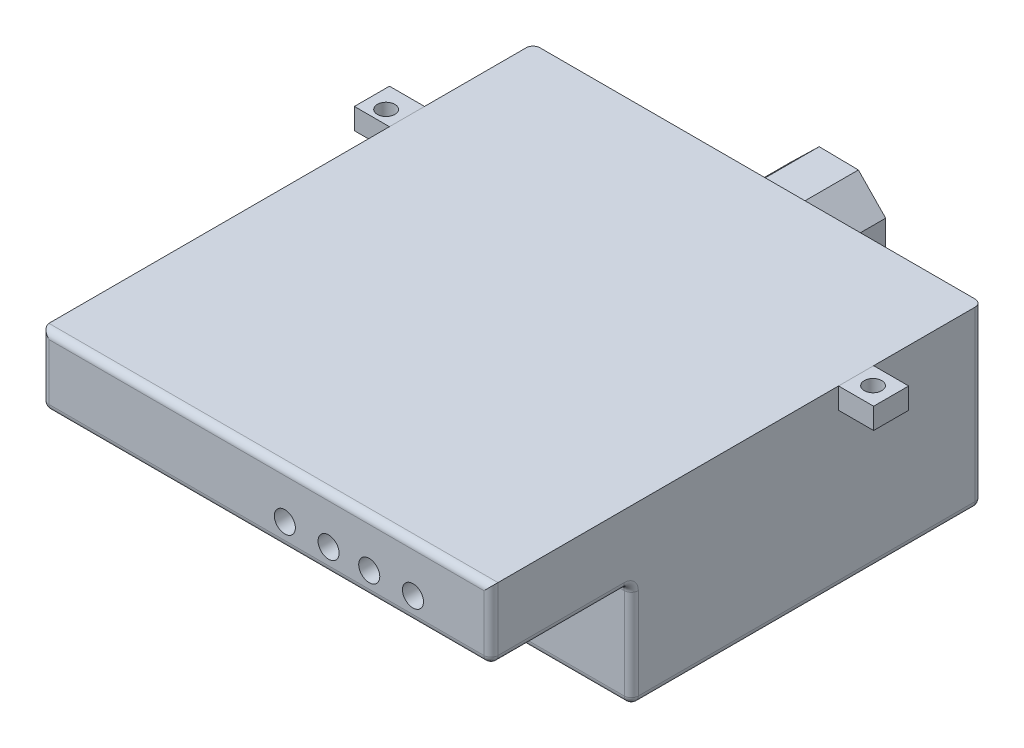
SolidWorks part; units mm, degrees
material "ABS PC"
ref_plane "Front Plane" through (0, 0, 0) normal (0, 0, 1) x (1, 0, 0)
ref_plane "Top Plane" through (0, 0, 0) normal (0, 1, 0) x (1, 0, 0)
ref_plane "Right Plane" through (0, 0, 0) normal (1, 0, 0) x (0, 0, -1)
sketch "Sketch1" plane through (0, 0, 0) normal (0, 1, 0) x (1, 0, 0)
  line L1 (0, 0) -> (64, 0)
  line L2 (0, 0) -> (0, 70)
  line L3 (0, 70) -> (64, 70)
  line L4 (64, 0) -> (64, 70)
  dimension "D1" = 70
  dimension "D2" = 64
extrude "Boss-Extrude1" add sketch "Sketch1" against normal blind 10
sketch "Sketch2" plane through (0, -10, 0) normal (0, -1, 0) x (1, 0, 0)
  line L0 (64, 0) -> (64, -70) construction
  line L1 (0, -70) -> (64, -70)
  line L2 (0, -70) -> (0, -20)
  line L3 (0, -20) -> (64, -20)
  line L4 (64, -70) -> (64, -20)
  dimension "D1" = 50
extrude "Boss-Extrude2" add sketch "Sketch2" along normal blind 15
fillet "Fillet1" radius 1 1 edges at (32, -25, -20)
fillet "Fillet2" radius 1 3 edges at (32, -25, -70) (32, -10, -20) (32, -10, 0)
fillet "Fillet3" radius 1 19 edges at (0, -12, -70) (0, -24.7071, -69.7071) (0, -24.7071, -20.2929) (0, -9.7071, -0.2929) (0, -10.2929, -19.7071) (64, -12, -70) (64, -24.7071, -69.7071) (64, -24.7071, -20.2929) (64, -9.7071, -0.2929) (64, -10.2929, -19.7071) (64, -4.5, 0) (32, 0, 0) (0, -4.5, 0) (0, -10, -10) (64, -10, -10) (64, -25, -45) (0, -25, -45) (0, -17.5, -20) (64, -17.5, -20)
sketch "Sketch9" plane through (0, 0, -70) normal (0, 0, -1) x (-1, 0, 0)
  line L1 (-34.3643, -4.3899) -> (-38.2548, -8.3953)
  line L2 (-38.2548, -8.3953) -> (-38.1735, -13.9785)
  line L3 (-38.1735, -13.9785) -> (-34.1681, -17.869)
  line L4 (-34.1681, -17.869) -> (-28.5849, -17.7877)
  line L5 (-28.5849, -17.7877) -> (-24.6944, -13.7823)
  line L6 (-24.6944, -13.7823) -> (-24.7757, -8.1991)
  line L7 (-24.7757, -8.1991) -> (-28.7811, -4.3086)
  line L8 (-28.7811, -4.3086) -> (-34.3643, -4.3899)
  circle A0 centre (-31.4746, -11.0888) radius 6.7403 construction
extrude "Boss-Extrude6" add sketch "Sketch9" along normal blind 12
sketch "Sketch11" plane through (0, 0, -82) normal (0, 0, -1) x (-1, 0, 0)
  circle A0 centre (-31.6839, -10.888) radius 5
  dimension "D1" = 10
extrude "Cut-Extrude2" cut sketch "Sketch11" against normal blind 12
sketch "Sketch12" plane through (0, -10, 0) normal (0, -1, 0) x (1, 0, 0)
  circle A0 centre (53.0034, -6.9382) radius 1.5
  circle A1 centre (46.6909, -6.9382) radius 1.5
  circle A2 centre (41.067, -6.9382) radius 1.5
  circle A3 centre (34.8693, -6.9382) radius 1.5
  dimension "D1" = 3
  dimension "D2" = 3
  dimension "D3" = 3
  dimension "D4" = 3
extrude "Cut-Extrude3" cut sketch "Sketch12" against normal blind 5
sketch "Sketch14" plane through (0, -10, 0) normal (0, -1, 0) x (1, 0, 0)
  line L1 (11.8542, -3.3764) -> (30.8021, -3.3764)
  line L2 (11.8542, -3.3764) -> (11.8542, -11.3258)
  line L3 (11.8542, -11.3258) -> (30.8021, -11.3258)
  line L4 (30.8021, -3.3764) -> (30.8021, -11.3258)
extrude "Boss-Extrude9" add sketch "Sketch14" along normal blind 3
chamfer "Chamfer1" distance 3 angle 45 1 edges at (11.8542, -13, -7.3511)
chamfer "Chamfer2" distance 2 angle 45 1 edges at (30.8021, -13, -7.3511)
fillet "Fillet4" radius 0.5 2 edges at (21.8282, -13, -11.3258) (21.8282, -13, -3.3764)
sketch "Sketch16" plane through (0, 0, 0) normal (0, 0, 1) x (1, 0, 0)
  circle A0 centre (34.6275, -6.6864) radius 1.5
  circle A1 centre (40.8593, -6.6864) radius 1.5
  circle A2 centre (46.6537, -6.6864) radius 1.5
  circle A3 centre (52.8854, -6.6864) radius 1.5
  dimension "D1" = 3
  dimension "D2" = 3
  dimension "D3" = 3
  dimension "D4" = 3
extrude "Cut-Extrude5" cut sketch "Sketch16" against normal blind 6.5
sketch "Sketch17" plane through (0, 0, 0) normal (0, 1, 0) x (1, 0, 0)
  line L0 (64, 1) -> (64, 69) construction
  line L1 (64, 49.5348) -> (69, 49.5348)
  line L2 (64, 49.5348) -> (64, 54.5348)
  line L3 (64, 54.5348) -> (69, 54.5348)
  line L4 (69, 49.5348) -> (69, 54.5348)
  line L5 (0, 69) -> (0, 1) construction
  line L6 (0, 49.5348) -> (-5, 49.5348)
  line L7 (0, 49.5348) -> (0, 54.5348)
  line L8 (0, 54.5348) -> (-5, 54.5348)
  line L9 (-5, 49.5348) -> (-5, 54.5348)
  dimension "D1" = 5
  dimension "D2" = 5
  dimension "D3" = 5
  dimension "D4" = 5
extrude "Boss-Extrude10" add sketch "Sketch17" against normal blind 3 separate body
sketch "Sketch18" plane through (0, -3, 0) normal (0, -1, 0) x (1, 0, 0)
  circle A0 centre (-2.3745, -51.4314) radius 1.25
  circle A1 centre (66.4213, -52.0348) radius 1.25
  dimension "D1" = 2.5
  dimension "D2" = 2.5
extrude "Cut-Extrude6" cut sketch "Sketch18" against normal through all both and the other way through all
sketch "Sketch21" plane through (0, -10, 0) normal (0, -1, 0) x (1, 0, 0)
  text T0 "v+ v-m+m-"
extrude "Boss-Extrude11" add sketch "Sketch21" along normal blind 0.5
